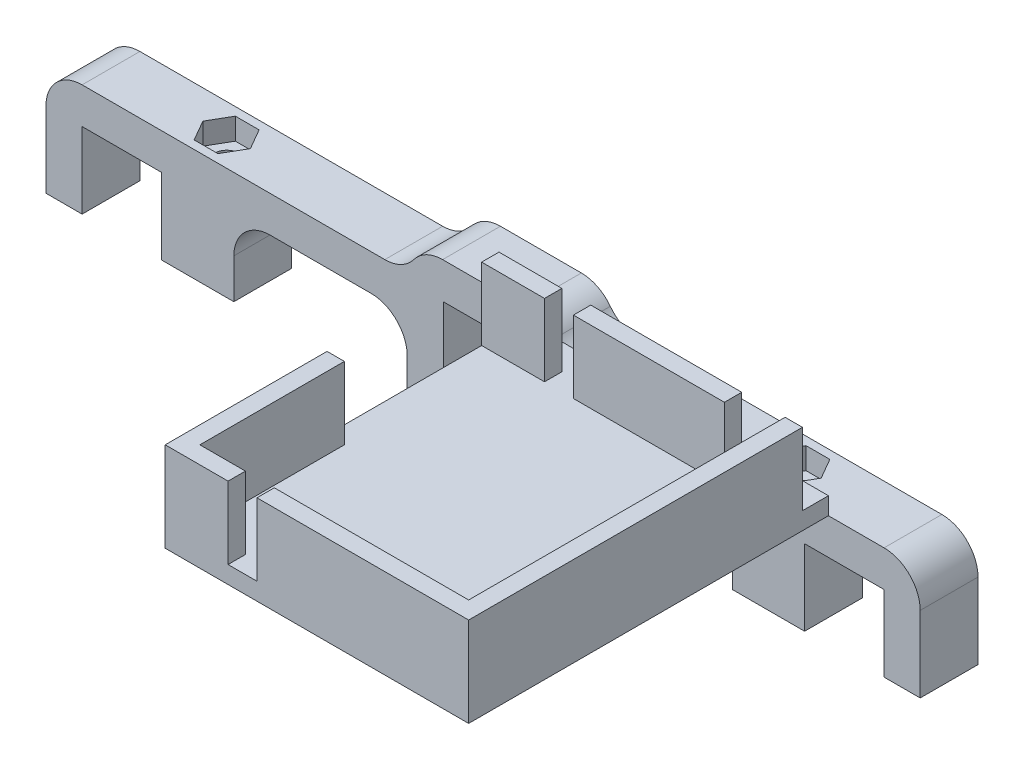
SolidWorks part; units mm, degrees
ref_plane "Plan de face" through (0, 0, 0) normal (0, 0, 1) x (1, 0, 0)
ref_plane "Plan de dessus" through (0, 0, 0) normal (0, 1, 0) x (1, 0, 0)
ref_plane "Plan de droite" through (0, 0, 0) normal (1, 0, 0) x (0, 0, -1)
sketch "Esquisse1" plane through (0, 0, 0) normal (0, 0, 1) x (1, 0, 0)
  line L0 (0, 10.5) -> (0, 15.5)
  line L1 (0, 0) -> (5, 0)
  line L2 (0, 0) -> (0, 10.5)
  line L3 (0, 10.5) -> (5, 10.5) construction
  line L4 (5, 0) -> (5, 10.5)
  line L5 (16, 0) -> (26, 0)
  line L6 (16, 0) -> (16, 10.5)
  line L7 (16, 10.5) -> (26, 10.5) construction
  line L8 (26, 0) -> (26, 10.5)
  line L9 (95, 0) -> (105, 0)
  line L10 (95, 0) -> (95, 10.5)
  line L11 (95, 10.5) -> (105, 10.5) construction
  line L12 (105, 0) -> (105, 10.5)
  line L13 (116, 0) -> (121, 0)
  line L14 (116, 0) -> (116, 10.5)
  line L15 (116, 10.5) -> (121, 10.5) construction
  line L16 (121, 0) -> (121, 10.5)
  line L17 (0, 15.5) -> (50, 15.5)
  line L18 (121, 15.5) -> (121, 10.5)
  line L19 (5, 10.5) -> (16, 10.5)
  line L20 (105, 10.5) -> (116, 10.5)
  line L21 (95, 10.5) -> (71, 10.5)
  line L22 (50, 10.5) -> (26, 10.5)
  line L24 (55, 10.5) -> (55, 14.5)
  line L25 (55, 14.5) -> (66, 14.5)
  line L26 (66, 10.5) -> (66, 14.5)
  line L27 (71, 15.5) -> (121, 15.5)
  line L29 (50, 15.5) -> (50, 19.5)
  line L30 (50, 19.5) -> (71, 19.5)
  line L31 (71, 15.5) -> (71, 19.5)
  line L32 (50, 10.5) -> (55, 10.5) construction
  line L34 (55, 10.5) -> (55, 0)
  line L35 (55, 0) -> (50, 0)
  line L36 (50, 10.5) -> (50, 0)
  line L38 (66, 10.5) -> (66, 0)
  line L39 (66, 0) -> (71, 0)
  line L40 (71, 10.5) -> (71, 0)
  line L41 (66, 10.5) -> (71, 10.5) construction
  dimension "D1" = 11
  dimension "D2" = 121
  dimension "D3" = 5
  dimension "D4" = 5
  dimension "D5" = 10.5
  dimension "D6" = 4
  dimension "D7" = 5
  dimension "D8" = 5
  dimension "D9" = 4
  dimension "D10" = 10
extrude "Boss.-Extru.1" add sketch "Esquisse1" along normal blind 8
sketch "Esquisse2" plane through (0, 15.5, 0) normal (0, 1, 0) x (1, 0, 0)
  line L1 (21, 0) -> (21, -8) construction
  line L2 (50, 0) -> (0, 0) construction
  line L3 (50, -8) -> (0, -8) construction
  line L4 (0, -8) -> (0, 0) construction
  line L5 (60.5, 0) -> (60.5, -8) construction
  line L6 (71, 0) -> (50, 0) construction
  line L7 (71, -8) -> (50, -8) construction
  circle A0 centre (21, -4) radius 1.65
  circle A1 centre (100, -4) radius 1.65
  point P10 (21, -4)
  dimension "D2" = 3.3
  dimension "D1" = 21
extrude "Enlèv. mat.-Extru.1" cut sketch "Esquisse2" against normal up to next
fillet "Congé1" radius 5 2 edges at (50, 19.5, 4) (71, 19.5, 4)
sketch "Esquisse3" plane through (0, 15.5, 0) normal (0, 1, 0) x (1, 0, 0)
  line L6 (19.3546, -1.15) -> (22.6454, -1.15)
  line L7 (22.6454, -1.15) -> (24.2909, -4)
  line L8 (24.2909, -4) -> (22.6454, -6.85)
  line L9 (22.6454, -6.85) -> (19.3546, -6.85)
  line L10 (19.3546, -6.85) -> (17.7091, -4)
  line L11 (17.7091, -4) -> (19.3546, -1.15)
  line L12 (19.3546, -1.15) -> (22.6454, -6.85) construction
  line L13 (60.5, 0) -> (60.5, -8) construction
  line L14 (66.101, 0) -> (54.899, 0) construction
  line L15 (66.101, -8) -> (54.899, -8) construction
  line L16 (101.6454, -1.15) -> (98.3546, -6.85) construction
  line L17 (103.2909, -4) -> (101.6454, -1.15)
  line L18 (101.6454, -6.85) -> (103.2909, -4)
  line L19 (98.3546, -6.85) -> (101.6454, -6.85)
  line L20 (96.7091, -4) -> (98.3546, -6.85)
  line L21 (98.3546, -1.15) -> (96.7091, -4)
  line L22 (101.6454, -1.15) -> (98.3546, -1.15)
  point P2 (21, -6.85)
  point P7 (21, -4)
  point P8 (21, -4)
  point P22 (100, -4)
  dimension "D1" = 5.7
  dimension "D2" = 5.7
  dimension "D3" = 120
extrude "Enlèv. mat.-Extru.2" cut sketch "Esquisse3" against normal blind 3
fillet "Congé2" radius 5 2 edges at (121, 15.5, 4) (0, 15.5, 4)
fillet "Congé3" radius 5 4 edges at (50, 10.5, 4) (95, 10.5, 4) (71, 10.5, 4) (26, 10.5, 4)
fillet "Congé4" radius 5 2 edges at (71, 15.5, 4) (50, 15.5, 4)
sketch "Esquisse4" plane through (0, 15.5, 0) normal (0, 1, 0) x (1, 0, 0)
  line L0 (116, -8) -> (74.101, -8) construction
  line L1 (66.3, -8) -> (105.3, -8)
  line L2 (66.3, -8) -> (66.3, -57.8)
  line L3 (66.3, -57.8) -> (105.3, -57.8)
  line L6 (121, 0) -> (121, -8) construction
  line L7 (105.3, -8) -> (108.3, -8)
  line L8 (105.3, -8) -> (105.3, -57.8) construction
  line L9 (105.3, -57.8) -> (108.3, -57.8)
  line L10 (108.3, -8) -> (108.3, -57.8)
  dimension "D1" = 15.7
  dimension "D2" = 49.8
  dimension "D3" = 3
  dimension "D4" = 39
extrude "Boss.-Extru.2" add sketch "Esquisse4" along normal blind 2.4 separate body
sketch "Esquisse5" plane through (0, 17.9, 0) normal (0, 1, 0) x (1, 0, 0)
  line L5 (66.3, -8) -> (66.3, -57.8) construction
  line L6 (66.3, -11.6) -> (108.3, -11.6)
  line L7 (66.3, -11.6) -> (66.3, -14)
  line L8 (66.3, -14) -> (108.3, -14)
  line L9 (108.3, -11.6) -> (108.3, -14)
  line L11 (116, -8) -> (74.101, -8) construction
  line L12 (108.3, -57.8) -> (108.3, -8) construction
  line L13 (66.3, -57.8) -> (108.3, -57.8) construction
  line L14 (108.3, -14) -> (105.9, -14)
  line L15 (108.3, -14) -> (108.3, -57.8)
  line L16 (108.3, -57.8) -> (105.9, -57.8)
  line L17 (105.9, -14) -> (105.9, -57.8)
  line L18 (66.3, -8) -> (66.3, -57.8) construction
  line L19 (105.9, -57.8) -> (66.3, -57.8)
  line L20 (105.9, -57.8) -> (105.9, -55.4)
  line L21 (105.9, -55.4) -> (66.3, -55.4)
  line L22 (66.3, -57.8) -> (66.3, -55.4)
  line L24 (66.3, -55.4) -> (68.7, -55.4)
  line L25 (66.3, -55.4) -> (66.3, -35.4)
  line L26 (66.3, -35.4) -> (68.7, -35.4)
  line L27 (68.7, -55.4) -> (68.7, -35.4)
  line M5 (66.3, -8) -> (66.3, -57.8)
  line M6 (66.3, -57.8) -> (108.3, -57.8)
  line M11 (108.3, -57.8) -> (108.3, -8)
  dimension "D1" = 2.4
  dimension "D2" = 6
  dimension "D3" = 2.4
  dimension "D4" = 2.4
  dimension "D5" = 2.4
  dimension "D6" = 20
extrude "Boss.-Extru.3" add sketch "Esquisse5" along normal blind 10 contours L8 L6 M5 M11 | L8 L17 M6 M11 | L20 L19 L22 L21 | L25 L24 L27 L26 region at (87.3, 17.9, 12.8) region at (107.1, 17.9, 35.9)
sketch "Esquisse9" plane through (0, 27.9, 0) normal (0, 1, 0) x (1, 0, 0)
  line L0 (108.3, -8) -> (66.3, -8) construction
  line L1 (75, -8) -> (79, -8)
  line L2 (75, -8) -> (75, -64.9734)
  line L3 (75, -64.9734) -> (79, -64.9734)
  line L4 (79, -8) -> (79, -64.9734)
  line L5 (66.3, -57.8) -> (66.3, -35.4) construction
  line L7 (99.9, -9.3649) -> (105.9, -9.3649)
  line L8 (99.9, -9.3649) -> (99.9, -16.9228)
  line L9 (99.9, -16.9228) -> (105.9, -16.9228)
  line L10 (105.9, -9.3649) -> (105.9, -16.9228)
  line L11 (108.3, -57.8) -> (108.3, -11.6) construction
  dimension "D1" = 8.7
  dimension "D2" = 4
  dimension "D3" = 2.4
  dimension "D4" = 6
extrude "Enlèv. mat.-Extru.3" cut sketch "Esquisse9" against normal up to surface (10 mm away) contours L2 L1 L4 L3 | L8 L7 L10 L9 up to face at (80.3, 17.9, 34.9333)
sketch "Esquisse10" plane through (0, 0, 8) normal (0, 0, 1) x (1, 0, 0)
  line L0 (95, 0) -> (105, 0) construction
  line L1 (66.3, 15.5) -> (105, 15.5)
  line L2 (66.3, 15.5) -> (66.3, 0)
  line L3 (66.3, 0) -> (71, 0)
  line L4 (105, 15.5) -> (105, 0)
  line L5 (105, 0) -> (105, 10.5) construction
  line L6 (95, 5.5) -> (95, 0) construction
  line L8 (71, 0) -> (71, 5.5)
  line L9 (76, 10.5) -> (90, 10.5)
  line L10 (95, 0) -> (95, 5.5)
  line L11 (76, 10.5) -> (90, 10.5) construction
  line L12 (95, 0) -> (105, 0)
  arc A0 (90, 10.5) -> (95, 5.5) centre (90, 5.5) cw
  arc A1 (71, 5.5) -> (76, 10.5) centre (76, 5.5) cw
  dimension "D1" = 5
extrude "Boss.-Extru.8" add sketch "Esquisse10" along normal up to surface (49.8 mm away) separate body contours L2 L3 L8 A1 L9 A0 L10 L12 L4 L1 rebuild error yes up to face at (82.15, 22.3, 57.8)
